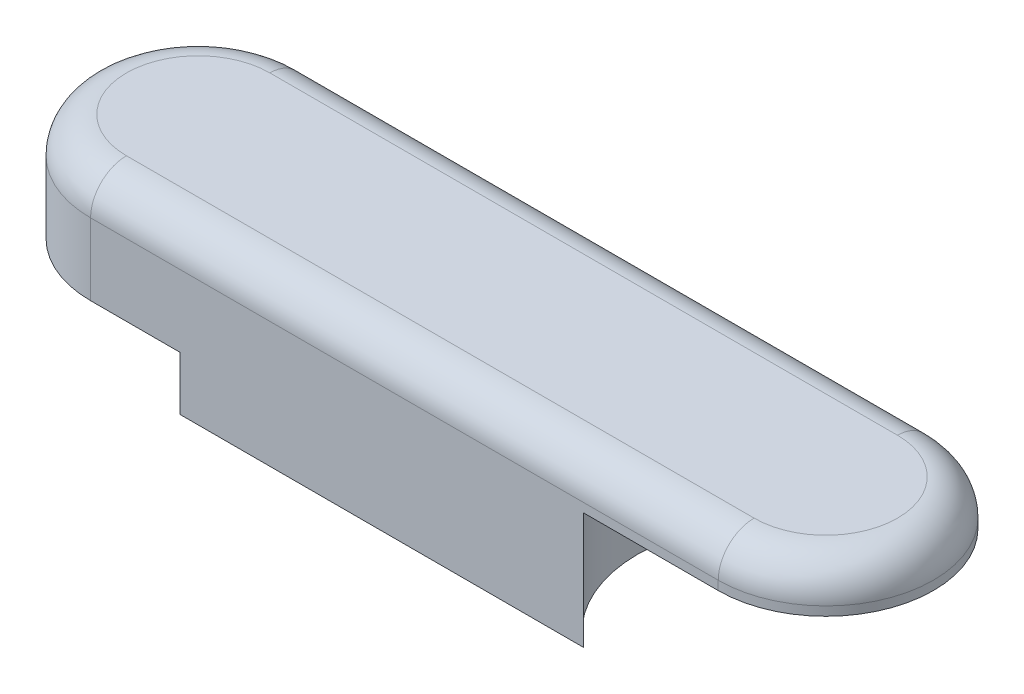
SolidWorks part; units mm, degrees
material "6061-T6 (SS)"
ref_plane "Ebene vorne" through (0, 0, 0) normal (0, 0, 1) x (1, 0, 0)
ref_plane "Ebene oben" through (0, 0, 0) normal (0, 1, 0) x (1, 0, 0)
ref_plane "Ebene rechts" through (0, 0, 0) normal (1, 0, 0) x (0, 0, -1)
sketch "Skizze2" plane through (0, 0, 0) normal (0, 1, 0) x (1, 0, 0)
  line L1 (0.3515, -60) -> (-350, -60)
  line L3 (0, 60) -> (-350, 60)
  arc A0 (0, -60) -> (0, 60) centre (0, 0) ccw
  arc A2 (-350, 60) -> (-350, -60) centre (-350, 0) ccw
  dimension "D1" = 120
  dimension "D4" = 120
  dimension "D2" = 350
  dimension "D3" = 60
extrude "Aufsatz-Linear austragen1" add sketch "Skizze2" along normal blind 45 and the other way blind 45 contours L3 A2 L1 A0 region at (-175, 0, 0)
sketch "Skizze3" plane through (0, 0, 60) normal (0, 0, 1) x (1, 0, 0)
  line L1 (60, -45) -> (-30, -45)
  line L2 (60, -45) -> (60, 20)
  line L3 (60, 20) -> (-30, 20)
  line L4 (-30, -45) -> (-30, 20)
  dimension "D1" = 90
  dimension "D2" = 65
extrude "Schnitt-Linear austragen1" cut sketch "Skizze3" against normal up to surface (120 mm away) up to face at (-175, 0, -60)
sketch "Skizze4" plane through (0, 20, 0) normal (0, -1, 0) x (1, 0, 0)
  circle A0 centre (0, 0) radius 25
  dimension "D1" = 50
extrude "Aufsatz-Linear austragen2" add sketch "Skizze4" along normal blind 20
sketch "Skizze5" plane through (0, -45, 0) normal (0, -1, 0) x (1, 0, 0)
  line L0 (-30, -60) -> (-30, 60) construction
  line L1 (-30, 0) -> (-30, 75) construction
  line L2 (-30, 0) -> (-30, -75) construction
  line L3 (-30, 75) -> (-30, -75)
  arc A0 (-30, 75) -> (-30, -75) centre (-30, 0) ccw
  dimension "D1" = 150
extrude "Schnitt-Linear austragen2" cut sketch "Skizze5" against normal up to surface (65 mm away) up to face at (-25, 20, 0)
sketch "Skizze6" plane through (0, 0, 60) normal (0, 0, 1) x (1, 0, 0)
  line L1 (-410, -45) -> (-300, -45)
  line L2 (-410, -45) -> (-410, -15)
  line L3 (-410, -15) -> (-300, -15)
  line L4 (-300, -45) -> (-300, -15)
  dimension "D1" = 110
  dimension "D2" = 30
extrude "Schnitt-Linear austragen3" cut sketch "Skizze6" against normal up to surface (120 mm away) up to face at (-141.6667, 6.6667, -60)
sketch "Skizze7" plane through (0, -45, 0) normal (0, -1, 0) x (-1, 0, 0)
  line L0 (300, 60) -> (300, -60) construction
  line L1 (300, -60) -> (300, 60)
  arc A0 (300, 60) -> (300, -60) centre (300, 0) ccw
  dimension "D1" = 120
extrude "Schnitt-Linear austragen4" cut sketch "Skizze7" against normal up to surface (30 mm away) up to face at (-340, -15, 0)
sketch "Skizze8" plane through (0, -15, 0) normal (0, -1, 0) x (-1, 0, 0)
  circle A0 centre (350, 0) radius 30
  dimension "D1" = 60
extrude "Aufsatz-Linear austragen3" add sketch "Skizze8" along normal blind 15
fillet "Verrundung1" radius 20 4 edges at (60, 45, 0) (-175, 45, 60) (-410, 45, 0) (-175, 45, -60)
